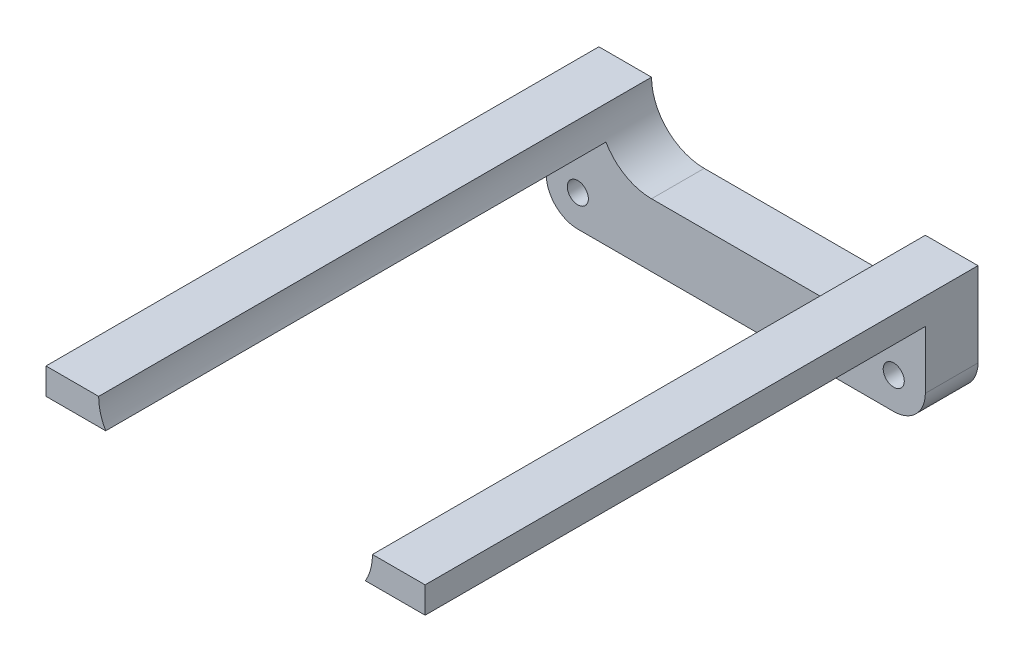
SolidWorks part; units mm, degrees
note: The reader was unsure of these and kept them because the rebuilt part matched: shared geometry of "Sketch1<3>".
material "Nylon 101"
ref_plane "Front" through (0, 0, 0) normal (0, 0, 1) x (1, 0, 0)
ref_plane "Top" through (0, 0, 0) normal (0, 1, 0) x (1, 0, 0)
ref_plane "Right" through (0, 0, 0) normal (1, 0, 0) x (0, 0, -1)
sketch "Sketch1" plane through (0, 0, 0) normal (0, 0, 1) x (1, 0, 0)
  line L0 (-30, 0) -> (30, 0) construction
  line L1 (-30, 6) -> (30, 6)
  line L2 (-30, -6) -> (30, -6)
  line L3 (-36, 0) -> (-36, 16)
  line L4 (-36, 16) -> (-26, 16)
  line L5 (-26, 16) -> (-26, 6)
  line L6 (36, 0) -> (36, 16)
  line L7 (36, 16) -> (26, 16)
  line L8 (26, 16) -> (26, 6)
  line L9 (-36, 11) -> (-26, 11)
  line L10 (26, 11) -> (36, 11)
  arc A0 (-30, 6) -> (-30, -6) centre (-30, 0) ccw
  arc A1 (30, -6) -> (30, 6) centre (30, 0) ccw
  circle A2 centre (-30, 0) radius 2
  circle A3 centre (30, 0) radius 2
  point P2 (0, 0)
  dimension "D2" = 4
  dimension "D3" = 6
  dimension "D1" = 60
  dimension "D4" = 10
  dimension "D5" = 10
  dimension "D6" = 5
  dimension "D7" = 5
extrude "Boss-Extrude1" add sketch "Sketch1" along normal mid plane 10
extrude "Boss-Extrude2" add sketch "Sketch1<3>" along normal blind 100 contours L3 L9 L5 L4 | L8 L10 L6 L7
sketch "Sketch1<3>" plane through (0, 0, 0) normal (0, 0, 1) x (1, 0, 0) same geometry as "Sketch1"
fillet "Fillet1" radius 10 2 edges at (26, 6, 0) (-26, 6, 0)
